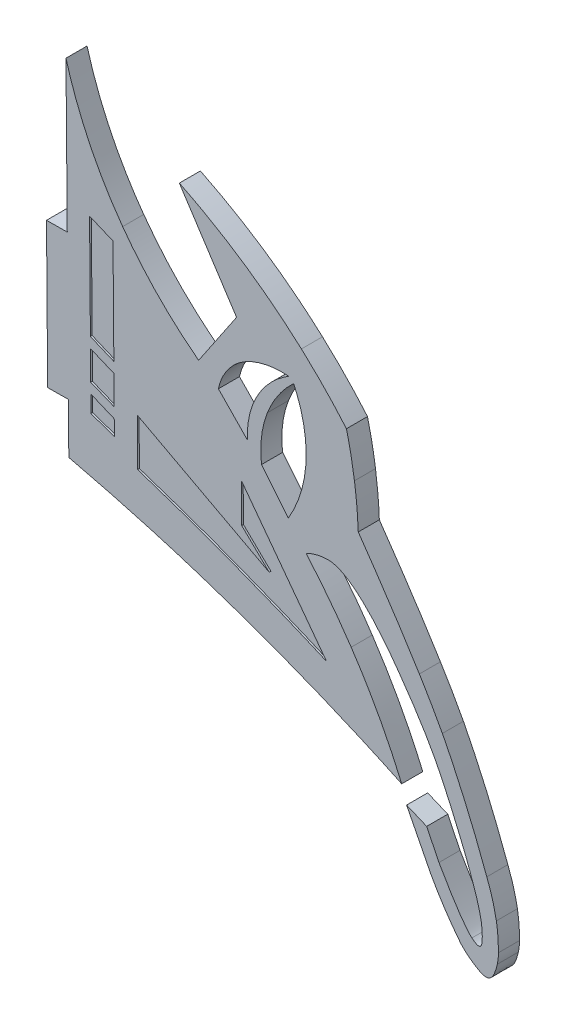
SolidWorks part; units mm, degrees
ref_plane "Front Plane" through (0, 0, 0) normal (0, 0, 1) x (1, 0, 0)
ref_plane "Top Plane" through (0, 0, 0) normal (0, 1, 0) x (1, 0, 0)
ref_plane "Right Plane" through (0, 0, 0) normal (1, 0, 0) x (0, 0, -1)
sketch "Model" plane through (0, 0, 0) normal (0, 0, 1) x (1, 0, 0)
  spline S0 degree 3 poles (88.982, 91.7609) (92.364, 86.9174) (99.8153, 76.1229) (106.3853, 65.4351) knots 0 0 0 0 1 1 1 1
  spline S1 degree 3 poles (106.3853, 65.4351) (108.6207, 61.7988) (110.5133, 58.5711) (112.9362, 54.0406) knots 0 0 0 0 1 1 1 1
  spline S2 degree 3 poles (112.9362, 54.0406) (112.9362, 54.0406) (119.2469, 42.2408) (125.5911, 24.9905) knots 0 0 0 0 1 1 1 1
  spline S3 degree 3 poles (125.5911, 24.9905) (127.0958, 21.1784) (127.8811, 17.9026) (128.3172, 15.4886) knots 0 0 0 0 1 1 1 1
  spline S4 degree 3 poles (128.3172, 15.4886) (128.4083, 14.9844) (128.9601, 11.8445) (128.9078, 7.9231) knots 0 0 0 0 1 1 1 1
  spline S5 degree 3 poles (128.9078, 7.9231) (128.8954, 6.9976) (128.8499, 6.0671) (128.5779, 4.9226) knots 0 0 0 0 1 1 1 1
  spline S6 degree 3 poles (128.5779, 4.9226) (128.2323, 3.4685) (127.6437, 0.956) (126.1859, 0.331) knots 0 0 0 0 1 1 1 1
  spline S7 degree 3 poles (126.1859, 0.331) (124.7305, -0.2929) (122.8539, 1.0439) (121.2129, 2.164) knots 0 0 0 0 1 1 1 1
  spline S8 degree 3 poles (121.2129, 2.164) (119.2926, 3.4746) (118.1798, 4.8592) (117.9986, 5.0884) knots 0 0 0 0 1 1 1 1
  spline S9 degree 3 poles (117.9986, 5.0884) (112.7297, 11.7522) (109.6154, 17.7807) (109.6154, 17.7807) knots 0 0 0 0 1 1 1 1
  spline S10 degree 3 poles (109.6154, 17.7807) (106.529, 23.7869) (104.139, 28.5176) (102.7496, 31.2788) knots 0 0 0 0 1 1 1 1
  spline S11 degree 3 poles (102.7496, 31.2788) (104.6552, 30.4801) (106.5609, 29.6814) (108.4665, 28.8826) knots 0 0 0 0 1 1 1 1
  spline S12 degree 3 poles (108.4665, 28.8826) (110.0397, 25.7269) (111.2479, 23.2175) (111.9691, 21.7068) knots 0 0 0 0 1 1 1 1
  spline S13 degree 3 poles (111.9691, 21.7068) (113.5915, 18.8507) (118.7386, 9.9257) (121.3559, 7.8015) knots 0 0 0 0 1 1 1 1
  spline S14 degree 3 poles (121.3559, 7.8015) (121.8094, 7.4334) (122.9199, 6.532) (123.6161, 6.8428) knots 0 0 0 0 1 1 1 1
  spline S15 degree 3 poles (123.6161, 6.8428) (124.0493, 7.0361) (124.1498, 7.6218) (124.1954, 7.9633) knots 0 0 0 0 1 1 1 1
  spline S16 degree 3 poles (124.1954, 7.9633) (124.6129, 11.0932) (123.7689, 14.5464) (123.493, 15.5969) knots 0 0 0 0 1 1 1 1
  spline S17 degree 3 poles (123.493, 15.5969) (123.1855, 16.767) (122.9118, 17.6997) (122.7253, 18.316) knots 0 0 0 0 1 1 1 1
  spline S18 degree 3 poles (122.7253, 18.316) (122.2165, 19.9974) (121.7133, 21.4054) (121.059, 23.2245) knots 0 0 0 0 1 1 1 1
  spline S19 degree 3 poles (121.059, 23.2245) (120.0248, 26.0995) (119.1518, 28.2391) (118.3238, 30.2738) knots 0 0 0 0 1 1 1 1
  spline S20 degree 3 poles (118.3238, 30.2738) (116.9028, 33.7658) (115.7209, 36.4259) (115.2046, 37.5753) knots 0 0 0 0 1 1 1 1
  spline S21 degree 3 poles (115.2046, 37.5753) (113.5668, 41.2209) (111.9697, 44.5765) (110.902, 46.5877) knots 0 0 0 0 1 1 1 1
  spline S22 degree 3 poles (110.902, 46.5877) (108.5064, 51.1002) (105.381, 56.1815) (100.4412, 63.0981) knots 0 0 0 0 1 1 1 1
  spline S23 degree 3 poles (100.4412, 63.0981) (88.3915, 79.9696) (82.4137, 80.5348) (80.5909, 80.5825) knots 0 0 0 0 1 1 1 1
  spline S24 degree 3 poles (80.5909, 80.5825) (77.8978, 80.653) (75.6423, 79.8197) (74.1102, 79.0653) knots 0 0 0 0 1 1 1 1
  spline S25 degree 3 poles (74.1102, 79.0653) (78.3105, 74.2555) (82.6951, 68.6849) (86.9649, 62.3185) knots 0 0 0 0 1 1 1 1
  spline S26 degree 3 poles (86.9649, 62.3185) (93.3628, 52.7789) (97.9849, 43.7158) (101.3551, 35.8159) knots 0 0 0 0 1 1 1 1
  spline S27 degree 3 poles (101.3551, 35.8159) (84.5382, 43.7809) (65.2989, 51.6812) (43.7309, 58.6142) knots 0 0 0 0 1 1 1 1
  spline S28 degree 3 poles (43.7309, 58.6142) (30.7351, 62.7916) (18.2849, 66.1707) (6.5286, 68.9127) knots 0 0 0 0 1 1 1 1
  spline S29 degree 3 poles (6.5286, 68.9127) (6.4906, 73.6686) (6.4526, 78.4245) (6.4145, 83.1804) knots 0 0 0 0 1 1 1 1
  spline S30 degree 3 poles (6.4145, 83.1804) (4.4437, 83.1646) (2.4729, 83.1488) (0.5021, 83.133) knots 0 0 0 0 1 1 1 1
  spline S31 degree 3 poles (0.5021, 83.133) (0.3925, 96.838) (0.2829, 110.5429) (0.1733, 124.2478) knots 0 0 0 0 1 1 1 1
  spline S32 degree 3 poles (0.1733, 124.2478) (2.1441, 124.2636) (4.1149, 124.2794) (6.0857, 124.2952) knots 0 0 0 0 1 1 1 1
  spline S33 degree 3 poles (6.0857, 124.2952) (5.9629, 138.5334) (5.8401, 152.7716) (5.7173, 167.0099) knots 0 0 0 0 1 1 1 1
  spline S34 degree 3 poles (5.7173, 167.0099) (8.0552, 158.6825) (12.6122, 146.3252) (21.8643, 133.5308) knots 0 0 0 0 1 1 1 1
  spline S35 degree 3 poles (21.8643, 133.5308) (29.3138, 123.2292) (37.3406, 116.055) (43.5078, 111.3599) knots 0 0 0 0 1 1 1 1
  spline S36 degree 3 poles (43.5078, 111.3599) (47.109, 116.7001) (50.7103, 122.0404) (54.3115, 127.3806) knots 0 0 0 0 1 1 1 1
  spline S37 degree 3 poles (54.3115, 127.3806) (48.8784, 135.701) (43.4453, 144.0213) (38.0122, 152.3416) knots 0 0 0 0 1 1 1 1
  spline S38 degree 3 poles (38.0122, 152.3416) (48.2704, 147.288) (60.667, 139.8158) (72.7848, 128.8107) knots 0 0 0 0 1 1 1 1
  spline S39 degree 3 poles (72.7848, 128.8107) (77.7474, 124.3038) (81.992, 119.8141) (85.6116, 115.5435) knots 0 0 0 0 1 1 1 1
  spline S40 degree 3 poles (85.6116, 115.5435) (86.4908, 111.9956) (87.2861, 108.0829) (87.8916, 103.8401) knots 0 0 0 0 1 1 1 1
  spline S41 degree 3 poles (87.8916, 103.8401) (88.5096, 99.5096) (88.8404, 95.4624) (88.982, 91.7609) knots 0 0 0 0 1 1 1 1
  spline S42 degree 3 poles (57.4234, 98.6361) (54.6622, 101.4775) (51.901, 104.3189) (49.1398, 107.1603) knots 0 0 0 0 1 1 1 1
  spline S43 degree 3 poles (49.1398, 107.1603) (49.5127, 108.8947) (50.5027, 112.1547) (53.4161, 115.0796) knots 0 0 0 0 1 1 1 1
  spline S44 degree 3 poles (53.4161, 115.0796) (59.3425, 121.0293) (68.0279, 120.3726) (69.176, 120.2682) knots 0 0 0 0 1 1 1 1
  spline S45 degree 3 poles (69.176, 120.2682) (67.1483, 119.0244) (63.6791, 116.5304) (60.9913, 112.287) knots 0 0 0 0 1 1 1 1
  spline S46 degree 3 poles (60.9913, 112.287) (57.3365, 106.5167) (57.2983, 100.9398) (57.4234, 98.6361) knots 0 0 0 0 1 1 1 1
  spline S47 degree 3 poles (70.5761, 119.1749) (68.5828, 117.3171) (65.2337, 113.7093) (63.1106, 108.2541) knots 0 0 0 0 1 1 1 1
  spline S48 degree 3 poles (63.1106, 108.2541) (60.8217, 102.3732) (61.0922, 97.26) (61.4308, 94.6184) knots 0 0 0 0 1 1 1 1
  spline S49 degree 3 poles (61.4308, 94.6184) (63.9734, 91.4889) (66.5161, 88.3594) (69.0588, 85.2299) knots 0 0 0 0 1 1 1 1
  spline S50 degree 3 poles (69.0588, 85.2299) (70.7398, 88.0625) (72.712, 92.2142) (73.6317, 97.4774) knots 0 0 0 0 1 1 1 1
  spline S51 degree 3 poles (73.6317, 97.4774) (75.381, 107.4884) (72.2776, 115.5406) (70.5761, 119.1749) knots 0 0 0 0 1 1 1 1
  spline S52 degree 3 poles (55.7777, 76.7379) (55.7483, 80.4194) (55.7188, 84.1008) (55.6894, 87.7823) knots 0 0 0 0 1 1 1 1
  spline S53 degree 3 poles (55.6894, 87.7823) (63.7705, 76.9656) (71.8516, 66.149) (79.9327, 55.3323) knots 0 0 0 0 1 1 1 1
  spline S54 degree 3 poles (79.9327, 55.3323) (71.7745, 58.881) (63.1963, 62.3976) (54.2053, 65.8248) knots 0 0 0 0 1 1 1 1
  spline S55 degree 3 poles (54.2053, 65.8248) (44.5489, 69.5057) (35.1766, 72.7937) (26.1422, 75.7353) knots 0 0 0 0 1 1 1 1
  spline S56 degree 3 poles (26.1422, 75.7353) (26.1066, 80.1928) (26.0709, 84.6502) (26.0353, 89.1077) knots 0 0 0 0 1 1 1 1
  spline S57 degree 3 poles (26.0353, 89.1077) (38.557, 82.451) (51.0788, 75.7944) (63.6005, 69.1378) knots 0 0 0 0 1 1 1 1
  spline S58 degree 3 poles (63.6005, 69.1378) (60.9929, 71.6712) (58.3853, 74.2046) (55.7777, 76.7379) knots 0 0 0 0 1 1 1 1
  spline S59 degree 3 poles (19.1211, 128.6061) (16.8941, 129.5393) (14.6671, 130.4726) (12.4402, 131.4059) knots 0 0 0 0 1 1 1 1
  spline S60 degree 3 poles (12.4402, 131.4059) (12.519, 121.546) (12.5979, 111.6862) (12.6768, 101.8264) knots 0 0 0 0 1 1 1 1
  spline S61 degree 3 poles (12.6768, 101.8264) (14.9037, 100.8931) (17.1307, 99.9599) (19.3576, 99.0266) knots 0 0 0 0 1 1 1 1
  spline S62 degree 3 poles (19.3576, 99.0266) (19.2788, 108.8865) (19.1999, 118.7463) (19.1211, 128.6061) knots 0 0 0 0 1 1 1 1
  spline S63 degree 3 poles (19.3813, 96.0687) (17.1544, 97.0019) (14.9274, 97.9352) (12.7004, 98.8684) knots 0 0 0 0 1 1 1 1
  spline S64 degree 3 poles (12.7004, 98.8684) (12.7225, 96.1074) (12.7446, 93.3463) (12.7667, 90.5852) knots 0 0 0 0 1 1 1 1
  spline S65 degree 3 poles (12.7667, 90.5852) (14.9934, 89.6826) (17.2201, 88.78) (19.4468, 87.8774) knots 0 0 0 0 1 1 1 1
  spline S66 degree 3 poles (19.4468, 87.8774) (19.425, 90.6079) (19.4031, 93.3383) (19.3813, 96.0687) knots 0 0 0 0 1 1 1 1
  spline S67 degree 3 poles (19.4705, 84.9195) (17.2435, 85.8528) (15.0166, 86.786) (12.7896, 87.7193) knots 0 0 0 0 1 1 1 1
  spline S68 degree 3 poles (12.7896, 87.7193) (12.8025, 86.1027) (12.8155, 84.4861) (12.8284, 82.8695) knots 0 0 0 0 1 1 1 1
  spline S69 degree 3 poles (12.8284, 82.8695) (15.0539, 82.1135) (17.2795, 81.3575) (19.505, 80.6015) knots 0 0 0 0 1 1 1 1
  spline S70 degree 3 poles (19.505, 80.6015) (19.4935, 82.0408) (19.482, 83.4802) (19.4705, 84.9195) knots 0 0 0 0 1 1 1 1
extrude "Boss-Extrude1" add sketch "Model" along normal blind 5.5 contours S61 S62 S59 S60 | S65 S66 S63 S64 | S69 S70 S67 S68 | S41 S40 S39 S38 S37 S36 S35 S34 S33 S32 S31 S30 S29 S28 S27 S26 S25 S24 S23 S22 S21 S20 S19 S18 S17 S16 S15 S14 S13 S12 S11 S10 S9 S8 S7 S6 S5 S4 S3 S2 S1 S0 S70 S69 S68 S67 S66 S65 S64 | S58 S57 S56 S55 S54 S53 S52 region at (53.6191, 89.0507, 0) region at (50.6453, 73.2572, 0) region at (15.8989, 115.2162, 0) region at (16.0676, 93.3525, 0) region at (16.0838, 84.0519, 0)
extrude "Boss-Extrude2" add sketch "Model<3>" along normal blind 6
sketch "Model<3>" plane through (0, 0, 0) normal (0, 0, 1) x (1, 0, 0) same geometry as "Model"
